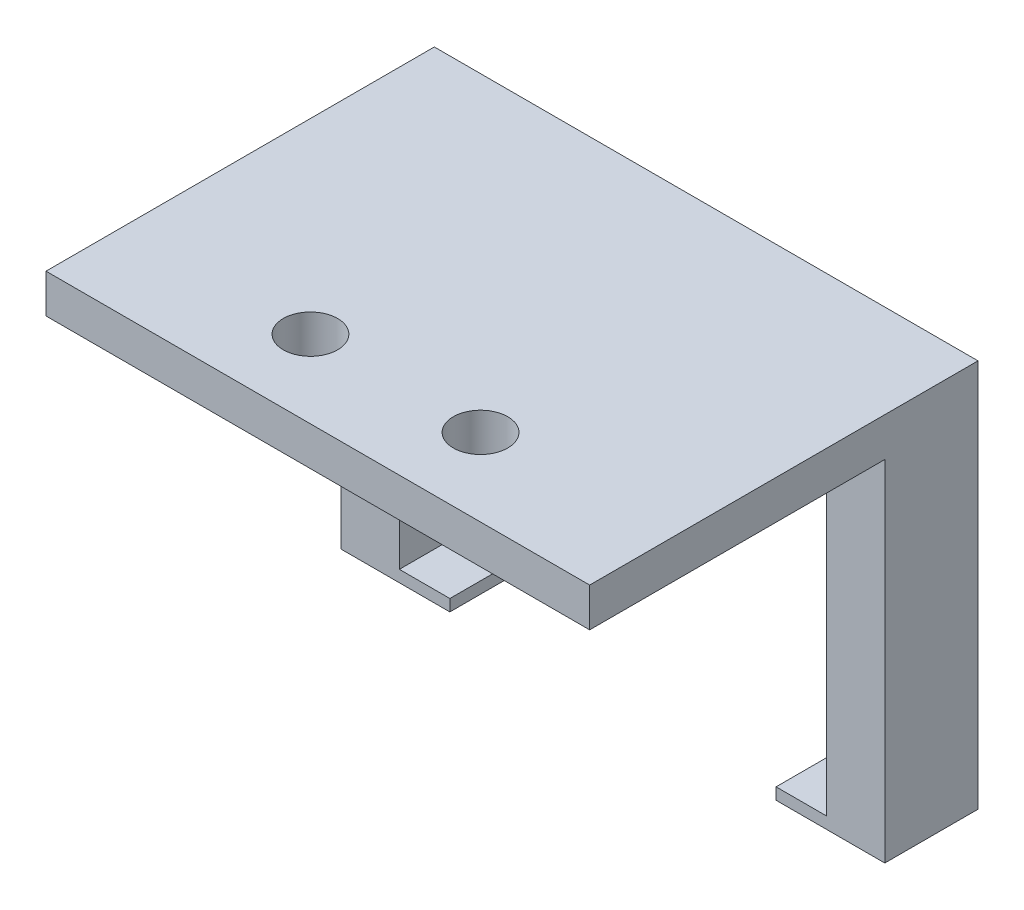
SolidWorks part; units mm, degrees
material "Custom Plastic"
ref_plane "Front Plane" through (0, 0, 0) normal (0, 0, 1) x (1, 0, 0)
ref_plane "Top Plane" through (0, 0, 0) normal (0, 1, 0) x (1, 0, 0)
ref_plane "Right Plane" through (0, 0, 0) normal (1, 0, 0) x (0, 0, -1)
sketch "Sketch3" plane through (0, 0, 0) normal (0, 1, 0) x (1, 0, 0)
  line L1 (-11.5173, 12.4673) -> (24.0427, 12.4673)
  line L2 (-11.5173, 12.4673) -> (-11.5173, -12.9327)
  line L3 (-11.5173, -12.9327) -> (24.0427, -12.9327)
  line L4 (24.0427, 12.4673) -> (24.0427, -12.9327)
  circle A0 centre (0.7001, -7.8527) radius 1.778
  circle A2 centre (11.8253, -7.8527) radius 1.778
  dimension "D2" = 3.556
  dimension "D3" = 3.556
  dimension "D1" = 25.4
  dimension "1" = 35.56
  dimension "D4" = 11.1252
  dimension "D5" = 12.2174
  dimension "D6" = 20.32
extrude "Boss-Extrude3" add sketch "Sketch3" along normal blind 2.54
sketch "Sketch4" plane through (0, 0, 0) normal (0, -1, 0) x (1, 0, 0)
  line L0 (-11.5173, -12.4673) -> (-11.5173, 12.9327) construction
  line L1 (-11.5173, -1.2913) -> (-7.7073, -1.2913)
  line L2 (-11.5173, -1.2913) -> (-11.5173, -12.4673)
  line L3 (-11.5173, -12.4673) -> (-7.7073, -12.4673)
  line L4 (-7.7073, -1.2913) -> (-7.7073, -12.4673)
  line L5 (24.0427, -12.4673) -> (-11.5173, -12.4673) construction
  line L6 (-11.5173, 12.9327) -> (24.0427, 12.9327) construction
  line L7 (24.0427, 12.9327) -> (24.0427, -12.4673) construction
  line L8 (24.0427, -1.2913) -> (20.2327, -1.2913)
  line L9 (24.0427, -1.2913) -> (24.0427, -12.4673)
  line L10 (24.0427, -12.4673) -> (20.2327, -12.4673)
  line L11 (20.2327, -1.2913) -> (20.2327, -12.4673)
  dimension "D1" = 14.224
  dimension "D2" = 3.81
  dimension "D3" = 14.224
  dimension "D4" = 3.81
extrude "Boss-Extrude4" add sketch "Sketch4" along normal blind 22.86
sketch "Sketch5" plane through (-7.7073, 0, 0) normal (1, 0, 0) x (0, 0, -1)
  line L0 (1.2913, -22.86) -> (1.2913, 0) construction
  line L1 (1.2913, -22.098) -> (12.4673, -22.098)
  line L2 (1.2913, -22.098) -> (1.2913, -22.86)
  line L3 (1.2913, -22.86) -> (12.4673, -22.86)
  line L4 (12.4673, -22.098) -> (12.4673, -22.86)
  dimension "D1" = 0.762
extrude "Boss-Extrude5" add sketch "Sketch5" along normal blind 3.302
sketch "Sketch6" plane through (20.2327, 0, 0) normal (-1, 0, 0) x (0, 0, 1)
  line L0 (-12.4673, 2.54) -> (-12.4673, -22.86) construction
  line L1 (-12.4673, -22.098) -> (-1.2913, -22.098)
  line L2 (-12.4673, -22.098) -> (-12.4673, -22.86)
  line L3 (-12.4673, -22.86) -> (-1.2913, -22.86)
  line L4 (-1.2913, -22.098) -> (-1.2913, -22.86)
  dimension "D1" = 0.762
extrude "Boss-Extrude6" add sketch "Sketch6" along normal blind 3.302
sketch "Sketch7" plane through (0, 0, -1.2913) normal (0, 0, 1) x (1, 0, 0)
  line L1 (-11.5173, 0) -> (24.0427, 0)
  line L2 (-11.5173, 0) -> (-11.5173, -22.86)
  line L3 (-11.5173, -22.86) -> (24.0427, -22.86)
  line L4 (24.0427, 0) -> (24.0427, -22.86)
extrude "Cut-Extrude1" cut sketch "Sketch7" against normal blind 5.08
